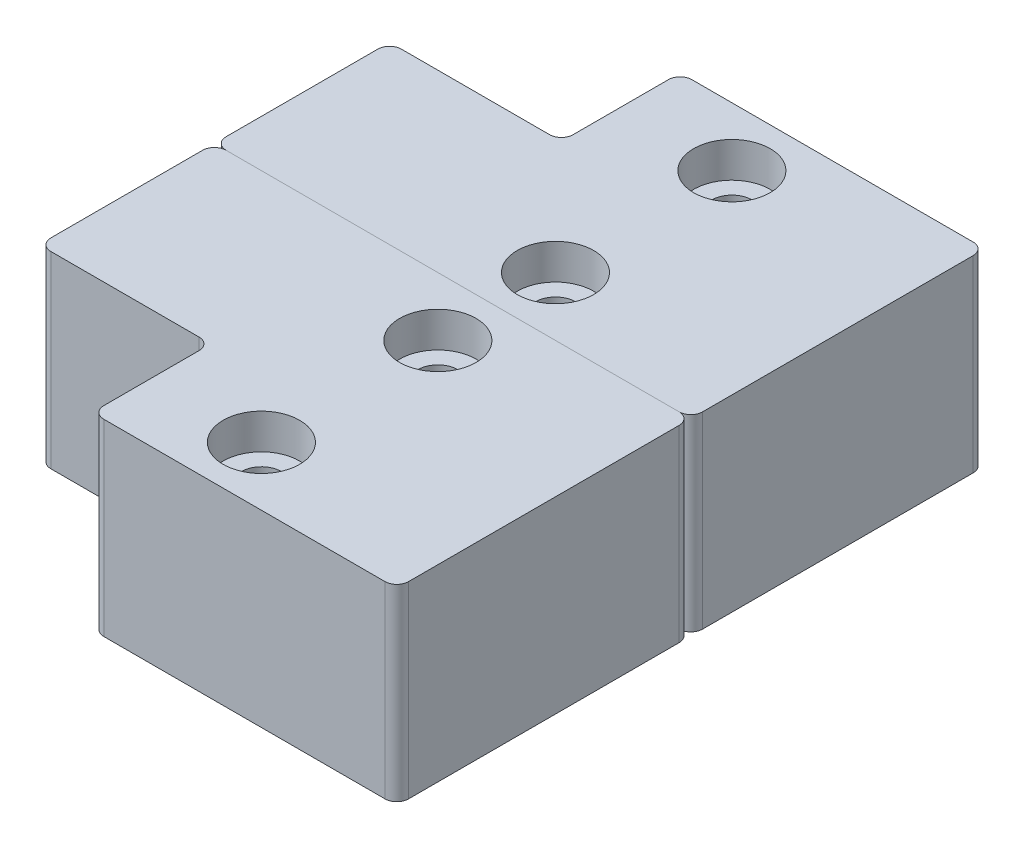
SolidWorks part; units mm, degrees
ref_plane "Front Plane" through (0, 0, 0) normal (0, 0, 1) x (1, 0, 0)
ref_plane "Top Plane" through (0, 0, 0) normal (0, 1, 0) x (1, 0, 0)
ref_plane "Right Plane" through (0, 0, 0) normal (1, 0, 0) x (0, 0, -1)
sketch "Sketch1" plane through (0, 0, 0) normal (0, 1, 0) x (1, 0, 0)
  line L0 (0, 0) -> (40.51, 0)
  line L1 (40.51, 0) -> (40.51, 25)
  line L2 (40.51, 25) -> (14.6, 25)
  line L3 (14.6, 25) -> (14.6, 14.9)
  line L4 (14.6, 14.9) -> (0, 14.9)
  line L5 (0, 14.9) -> (0, 0)
  dimension "D1" = 40.51
  dimension "D2" = 25
  dimension "D3" = 14.6
  dimension "D4" = 10.1
extrude "Boss-Extrude1" add sketch "Sketch1" along normal blind 16
fillet "Fillet1" radius 1 6 edges at (0, 8, -14.9) (14.6, 8, -14.9) (14.6, 8, -25) (40.51, 8, -25) (40.51, 8, 0) (0, 8, 0)
sketch "Sketch2" plane through (0, 16, 0) normal (0, 1, 0) x (1, 0, 0)
  line L0 (24, 25) -> (24, 0) construction
  line L1 (39.51, 25) -> (15.6, 25) construction
  line L2 (1, 0) -> (39.51, 0) construction
  line L3 (40.51, 1) -> (40.51, 24) construction
  line L4 (40.51, 12.5) -> (0, 12.5) construction
  line L5 (0, 13.9) -> (0, 1) construction
  point P12 (24, 20)
  point P13 (24, 5)
  point P14 (24, 12.5)
  dimension "D1" = 16.51
  dimension "D2" = 15
  dimension "D3" = 7.5
hole_wizard "CBORE for M3 SHCS1" positions "Sketch3" profile "Sketch4" counterbore size "M3" standard "ANSI Metric" end condition up to next
sketch "Sketch3" plane through (0, 16, 0) normal (0, 1, 0) x (1, 0, 0)
  point P0 (24, 20)
  point P3 (24, 5)
sketch "Sketch4" plane through (24, 16, -20) normal (1, 0, 0) x (0, 0, 1)
  line L0 (0, 0) -> (0, 16)
  line L1 (0, 16) -> (1.7, 16)
  line L3 (1.7, 16) -> (1.7, 3)
  line L4 (1.7, 3) -> (3.25, 3)
  line L5 (3.25, 3) -> (3.25, 0)
  line L7 (3.25, 0) -> (0, 0)
  line L11 (0, -6.35) -> (0, 107.95) construction
  dimension "Thru Hole Dia." = 3.4
  dimension "Thru Hole Depth" = 16
  dimension "C'Bore Dia." = 6.5
  dimension "C'Bore Depth" = 3
mirror "Mirror1" about plane through (0, 16, 0) normal (0, 0, -1) of bodies 102
